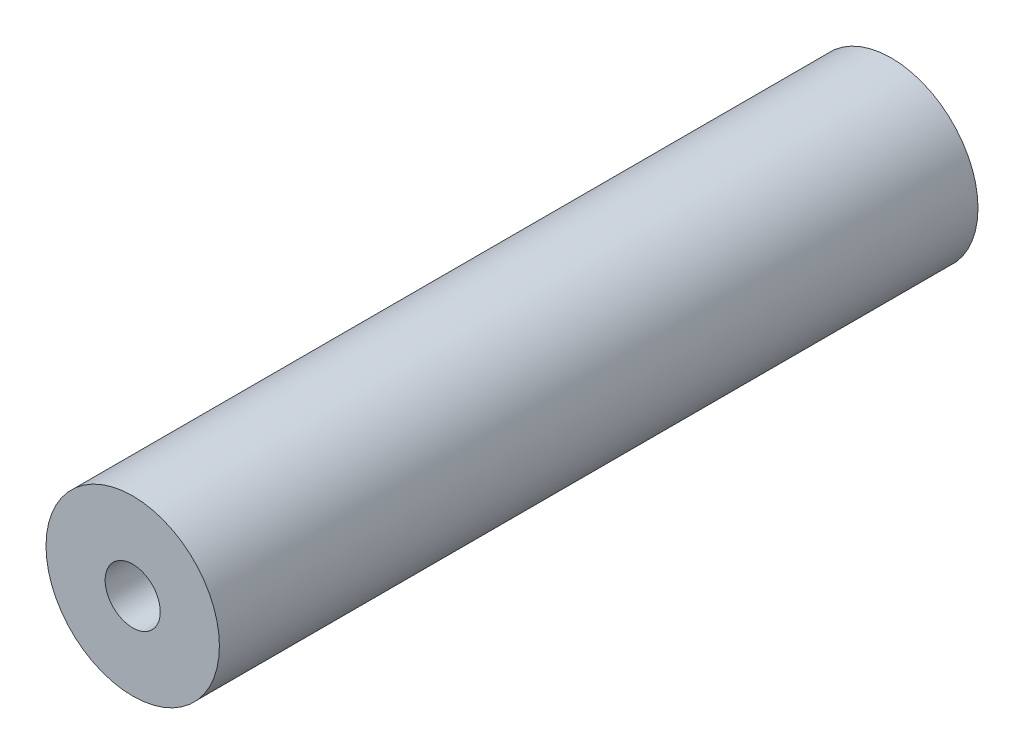
SolidWorks part; units mm, degrees
ref_plane "Front Plane" through (0, 0, 0) normal (0, 0, 1) x (1, 0, 0)
ref_plane "Top Plane" through (0, 0, 0) normal (0, 1, 0) x (1, 0, 0)
ref_plane "Right Plane" through (0, 0, 0) normal (1, 0, 0) x (0, 0, -1)
sketch "Sketch1" plane through (0, 0, 0) normal (0, 0, 1) x (1, 0, 0)
  circle A1 centre (0, 0) radius 6.35
  dimension "D2" = 12.7
extrude "Boss-Extrude1" add sketch "Sketch1" along normal mid plane 55.5625 contours A1 region at (0, 0, 0)
hole_wizard "#10-32 Tapped Hole1" positions "3DSketch1" profile "Sketch2" tap size "#10-32" standard "ANSI Inch"
sketch3d "3DSketch1"
  line L0 (0, 0, 27.7812) -> (0, 0, -27.7812) construction
  point P0 (0, 0, 27.7812)
  point P4 (0, 0, -27.7812)
sketch "Sketch2" plane through (0, 0, 27.7812) normal (1, 0, 0) x (0, -1, 0)
  line L0 (0, 0) -> (0, 13.2428)
  line L1 (0, 13.2428) -> (2.0193, 12.0294)
  line L2 (2.0193, 12.0294) -> (2.0193, 0)
  line L5 (2.0193, 0) -> (0, 0)
  line L10 (0, 13.2428) -> (-2.0193, 12.0294) construction
  line L11 (0, -6.35) -> (0, 107.95) construction
  dimension "Tap Drill Dia." = 4.0386
  dimension "Tap Drill Depth" = 12.0294
  dimension "Drill Angle" = 118
cosmetic thread "Hole Thread1" parameters "D1"=9.652, "D2"=4.826
cosmetic thread "Hole Thread2" parameters "D1"=9.652, "D2"=4.826
